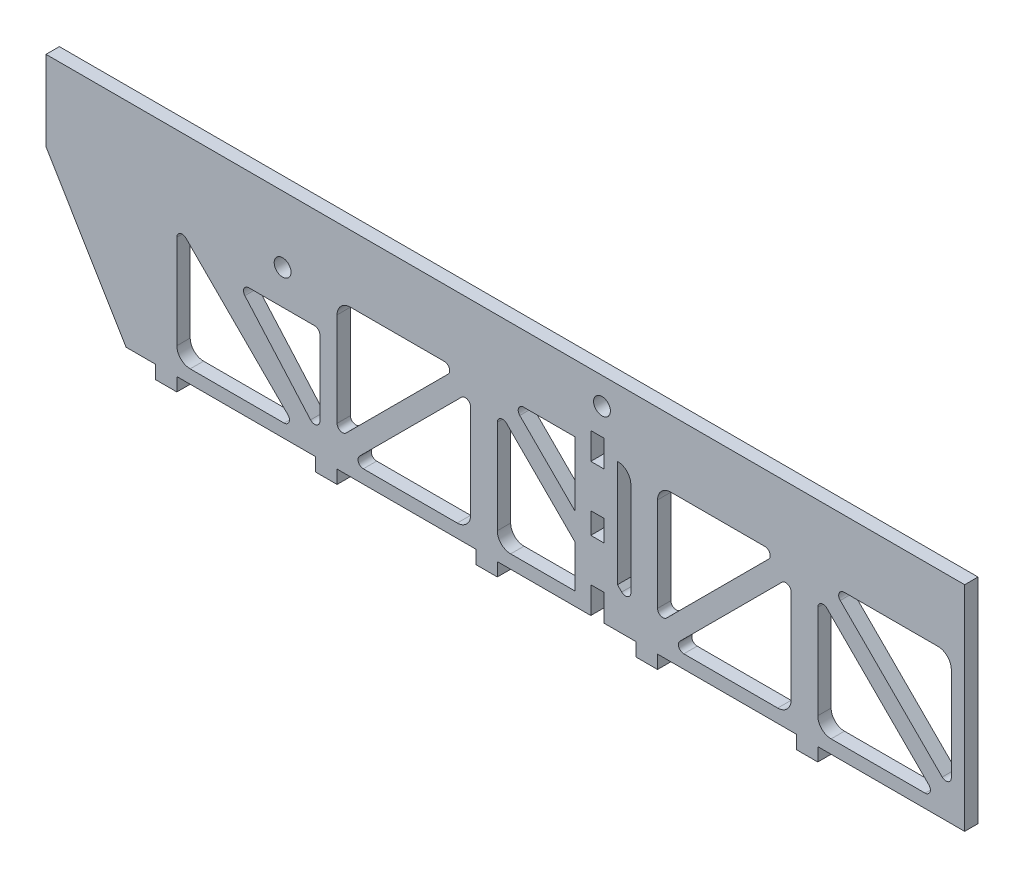
SolidWorks part; units mm, degrees
material "Pine"
ref_plane "Front Plane" through (0, 0, 0) normal (0, 0, 1) x (1, 0, 0)
ref_plane "Top Plane" through (0, 0, 0) normal (0, 1, 0) x (1, 0, 0)
ref_plane "Right Plane" through (0, 0, 0) normal (1, 0, 0) x (0, 0, -1)
sketch "Model" plane through (0, 0, 0) normal (0, 0, 1) x (1, 0, 0)
  line L0 (-306.6281, 15.625) -> (-306.6281, 51.1493)
  line L1 (-309.1681, 53.6893) -> (-340.406, 53.6893)
  line L2 (-342.3135, 49.472) -> (-311.0755, 13.9477)
  line L8 (-171.2321, 6.35) -> (-215.9, 6.35)
  line L9 (-222.25, 57.3679) -> (-222.25, 12.7)
  line L10 (-217.9139, 59.1639) -> (-169.4361, 10.6861)
  line L11 (-234.95, 57.3679) -> (-234.95, 12.7)
  line L12 (-241.3, 6.35) -> (-285.9679, 6.35)
  line L13 (-239.2861, 59.1639) -> (-287.7639, 10.6861)
  line L14 (-294.1139, 17.0361) -> (-245.6361, 65.5139)
  line L15 (-298.45, 63.5) -> (-298.45, 18.8321)
  line L16 (-247.4321, 69.85) -> (-292.1, 69.85)
  line L17 (-323.6321, 6.35) -> (-368.3, 6.35)
  line L18 (-374.65, 57.3679) -> (-374.65, 12.7)
  line L19 (-370.3139, 59.1639) -> (-321.8361, 10.6861)
  line L20 (-18.8321, 6.35) -> (-63.5, 6.35)
  line L21 (-69.85, 57.3679) -> (-69.85, 12.7)
  line L22 (-17.0361, 10.6861) -> (-65.5139, 59.1639)
  line L23 (-82.55, 57.3679) -> (-82.55, 12.7)
  line L24 (-88.9, 6.35) -> (-133.5679, 6.35)
  line L25 (-86.8861, 59.1639) -> (-135.3639, 10.6861)
  line L26 (-93.2361, 65.5139) -> (-141.7139, 17.0361)
  line L27 (-146.05, 63.5) -> (-146.05, 18.8321)
  line L28 (-95.0321, 69.85) -> (-139.7, 69.85)
  line L29 (-163.0861, 17.0361) -> (-211.5639, 65.5139)
  line L30 (-165.1, 69.85) -> (-209.7679, 69.85)
  line L31 (-158.75, 63.5) -> (-158.75, 18.8321)
  line L35 (-398.78, 0) -> (-436.88, 63.5)
  line L36 (0, 0) -> (-398.78, 0)
  line L37 (0, 0) -> (0, 95.25)
  line L38 (0, 95.25) -> (-436.88, 95.25)
  line L39 (-436.88, 63.5) -> (-436.88, 95.25)
  line L40 (-6.35, 63.5) -> (-6.35, 18.8321)
  line L41 (-59.1639, 65.5139) -> (-10.6861, 17.0361)
  line L42 (-12.7, 69.85) -> (-57.3679, 69.85)
  arc A0 (-222.25, 12.7) -> (-215.9, 6.35) centre (-215.9, 12.7) ccw
  arc A1 (-217.9139, 59.1639) -> (-222.25, 57.3679) centre (-219.71, 57.3679) ccw
  arc A2 (-171.2321, 6.35) -> (-169.4361, 10.6861) centre (-171.2321, 8.89) ccw
  arc A3 (-234.95, 57.3679) -> (-239.2861, 59.1639) centre (-237.49, 57.3679) ccw
  arc A4 (-241.3, 6.35) -> (-234.95, 12.7) centre (-241.3, 12.7) ccw
  arc A5 (-287.7639, 10.6861) -> (-285.9679, 6.35) centre (-285.9679, 8.89) ccw
  arc A6 (-245.6361, 65.5139) -> (-247.4321, 69.85) centre (-247.4321, 67.31) ccw
  arc A7 (-298.45, 18.8321) -> (-294.1139, 17.0361) centre (-295.91, 18.8321) ccw
  arc A8 (-292.1, 69.85) -> (-298.45, 63.5) centre (-292.1, 63.5) ccw
  arc A9 (-323.6321, 6.35) -> (-321.8361, 10.6861) centre (-323.6321, 8.89) ccw
  arc A10 (-374.65, 12.7) -> (-368.3, 6.35) centre (-368.3, 12.7) ccw
  arc A11 (-370.3139, 59.1639) -> (-374.65, 57.3679) centre (-372.11, 57.3679) ccw
  arc A12 (-69.85, 12.7) -> (-63.5, 6.35) centre (-63.5, 12.7) ccw
  arc A13 (-65.5139, 59.1639) -> (-69.85, 57.3679) centre (-67.31, 57.3679) ccw
  arc A14 (-18.8321, 6.35) -> (-17.0361, 10.6861) centre (-18.8321, 8.89) ccw
  arc A15 (-82.55, 57.3679) -> (-86.8861, 59.1639) centre (-85.09, 57.3679) ccw
  arc A16 (-88.9, 6.35) -> (-82.55, 12.7) centre (-88.9, 12.7) ccw
  arc A17 (-135.3639, 10.6861) -> (-133.5679, 6.35) centre (-133.5679, 8.89) ccw
  arc A18 (-93.2361, 65.5139) -> (-95.0321, 69.85) centre (-95.0321, 67.31) ccw
  arc A19 (-146.05, 18.8321) -> (-141.7139, 17.0361) centre (-143.51, 18.8321) ccw
  arc A20 (-139.7, 69.85) -> (-146.05, 63.5) centre (-139.7, 63.5) ccw
  arc A21 (-163.0861, 17.0361) -> (-158.75, 18.8321) centre (-161.29, 18.8321) ccw
  arc A22 (-209.7679, 69.85) -> (-211.5639, 65.5139) centre (-209.7679, 67.31) ccw
  arc A23 (-158.75, 63.5) -> (-165.1, 69.85) centre (-165.1, 63.5) ccw
  arc A24 (-306.6281, 15.625) -> (-311.0755, 13.9477) centre (-309.1681, 15.625) cw
  arc A25 (-340.406, 53.6893) -> (-342.3135, 49.472) centre (-340.406, 51.1493) ccw
  arc A26 (-306.6281, 51.1493) -> (-309.1681, 53.6893) centre (-309.1681, 51.1493) ccw
  arc A27 (-10.6861, 17.0361) -> (-6.35, 18.8321) centre (-8.89, 18.8321) ccw
  arc A28 (-57.3679, 69.85) -> (-59.1639, 65.5139) centre (-57.3679, 67.31) ccw
  arc A29 (-6.35, 63.5) -> (-12.7, 69.85) centre (-12.7, 63.5) ccw
  circle A30 centre (-172.466, 88.9) radius 4
  circle A31 centre (-324.358, 70.104) radius 4
  dimension "D2" = 172.466
  dimension "D4" = 8
  dimension "D5" = 151.892
  dimension "D7" = 8
  dimension "D6" = 18.796
  dimension "D8" = 2.54
  dimension "D1" = 95.25
  dimension "D3" = 6.35
extrude "Boss-Extrude1" add sketch "Model" along normal blind 6.35
sketch "Sketch1" plane through (0, 0, 6.35) normal (0, 0, 1) x (1, 0, 0)
  line L0 (-69.85, 95.25) -> (-69.85, 0) construction
  line L1 (-69.85, 57.3679) -> (-69.85, 12.7) construction
  line L2 (-398.78, 0) -> (0, 0) construction
  line L3 (-146.05, 95.25) -> (-146.05, 0) construction
  line L4 (-146.05, 63.5) -> (-146.05, 18.8321) construction
  line L5 (-222.25, 95.25) -> (-222.25, 0) construction
  line L6 (-222.25, 57.3679) -> (-222.25, 12.7) construction
  line L7 (-298.45, 95.25) -> (-298.45, 0) construction
  line L8 (-298.45, 63.5) -> (-298.45, 18.8321) construction
  line L9 (-374.65, 95.25) -> (-374.65, 0) construction
  line L10 (-374.65, 57.3679) -> (-374.65, 12.7) construction
  line L11 (0, 95.25) -> (-436.88, 95.25) construction
  line L12 (-69.85, 0) -> (-80.01, 0)
  line L13 (-69.85, 0) -> (-69.85, -6.35)
  line L14 (-69.85, -6.35) -> (-80.01, -6.35)
  line L15 (-80.01, 0) -> (-80.01, -6.35)
  line L16 (-146.05, 0) -> (-156.21, 0)
  line L17 (-146.05, 0) -> (-146.05, -6.35)
  line L18 (-146.05, -6.35) -> (-156.21, -6.35)
  line L19 (-156.21, 0) -> (-156.21, -6.35)
  line L20 (-222.25, 0) -> (-232.41, 0)
  line L21 (-222.25, 0) -> (-222.25, -6.35)
  line L22 (-222.25, -6.35) -> (-232.41, -6.35)
  line L23 (-232.41, 0) -> (-232.41, -6.35)
  line L24 (-298.45, 0) -> (-308.61, 0)
  line L25 (-298.45, 0) -> (-298.45, -6.35)
  line L26 (-298.45, -6.35) -> (-308.61, -6.35)
  line L27 (-308.61, 0) -> (-308.61, -6.35)
  line L28 (-374.65, 0) -> (-384.81, 0)
  line L29 (-374.65, 0) -> (-374.65, -6.35)
  line L30 (-374.65, -6.35) -> (-384.81, -6.35)
  line L31 (-384.81, 0) -> (-384.81, -6.35)
  line L32 (0, 0) -> (0, 95.25) construction
  line L53 (-436.88, 95.25) -> (0, 95.25)
  line L54 (-436.88, 95.25) -> (-436.88, 101.6)
  line L55 (-436.88, 101.6) -> (0, 101.6)
  line L56 (0, 95.25) -> (0, 101.6)
  dimension "D1" = 6.35
  dimension "D2" = 10.16
  dimension "D3" = 10.16
  dimension "D4" = 10.16
  dimension "D5" = 10.16
  dimension "D6" = 10.16
  dimension "D8" = 6.35
extrude "Boss-Extrude2" add sketch "Sketch1" against normal up to surface (6.35 mm away) up to face at (-168.466, 88.9, 0)
sketch "Sketch2" plane through (0, 0, 0) normal (0, 0, -1) x (-1, 0, 0)
  line L0 (158.75, 18.8321) -> (158.75, 63.5) construction
  line L1 (185.42, 69.85) -> (165.1, 69.85)
  line L2 (185.42, 69.85) -> (185.42, 0)
  line L3 (185.42, 0) -> (165.1, 0)
  line L4 (165.1, 69.85) -> (165.1, 0)
  line L6 (222.25, 0) -> (156.21, 0) construction
  line L8 (165.1, 69.85) -> (209.7679, 69.85) construction
  line L10 (156.21, -6.35) -> (146.05, -6.35) construction
  line L11 (177.8, 0) -> (171.45, 0)
  line L12 (177.8, 0) -> (177.8, 12.7)
  line L13 (177.8, 12.7) -> (171.45, 12.7)
  line L14 (171.45, 0) -> (171.45, 12.7)
  line L15 (177.8, 33.02) -> (171.45, 33.02)
  line L16 (177.8, 33.02) -> (177.8, 43.18)
  line L17 (177.8, 43.18) -> (171.45, 43.18)
  line L18 (171.45, 33.02) -> (171.45, 43.18)
  line L19 (177.8, 63.5) -> (171.45, 63.5)
  line L20 (177.8, 63.5) -> (177.8, 76.2)
  line L21 (177.8, 76.2) -> (171.45, 76.2)
  line L22 (171.45, 63.5) -> (171.45, 76.2)
  dimension "D1" = 6.35
  dimension "D2" = 20.32
  dimension "D3" = 10.16
  dimension "D4" = 12.7
  dimension "D5" = 6.35
  dimension "D6" = 20.32
  dimension "D7" = 20.32
  dimension "D8" = 12.7
  dimension "D9" = 6.35
  dimension "D10" = 6.35
extrude "Boss-Extrude3" add sketch "Sketch2" against normal up to surface (6.35 mm away) contours L4 | L19 L22 L1 L4 L3 L14 L13 L12 L2 L20 L15 L18 L17 L16 region at (-184.6925, 34.925, 0) up to face at (-319.4123, 39.5294, 6.35)
extrude "Cut-Extrude1" cut sketch "Sketch2<3>" against normal blind 6.35 contours L22 L1 L20 L21 | L14 L3 L12 L13 region at (-174.625, 73.025, 0) region at (-174.625, 6.35, 0)
sketch "Sketch2<3>" plane through (0, 0, 0) normal (0, 0, -1) x (-1, 0, 0) same geometry as "Sketch2"
equation "\"thick\"=0.25"
equation "\"D1@Boss-Extrude1\"=\"thick\""
